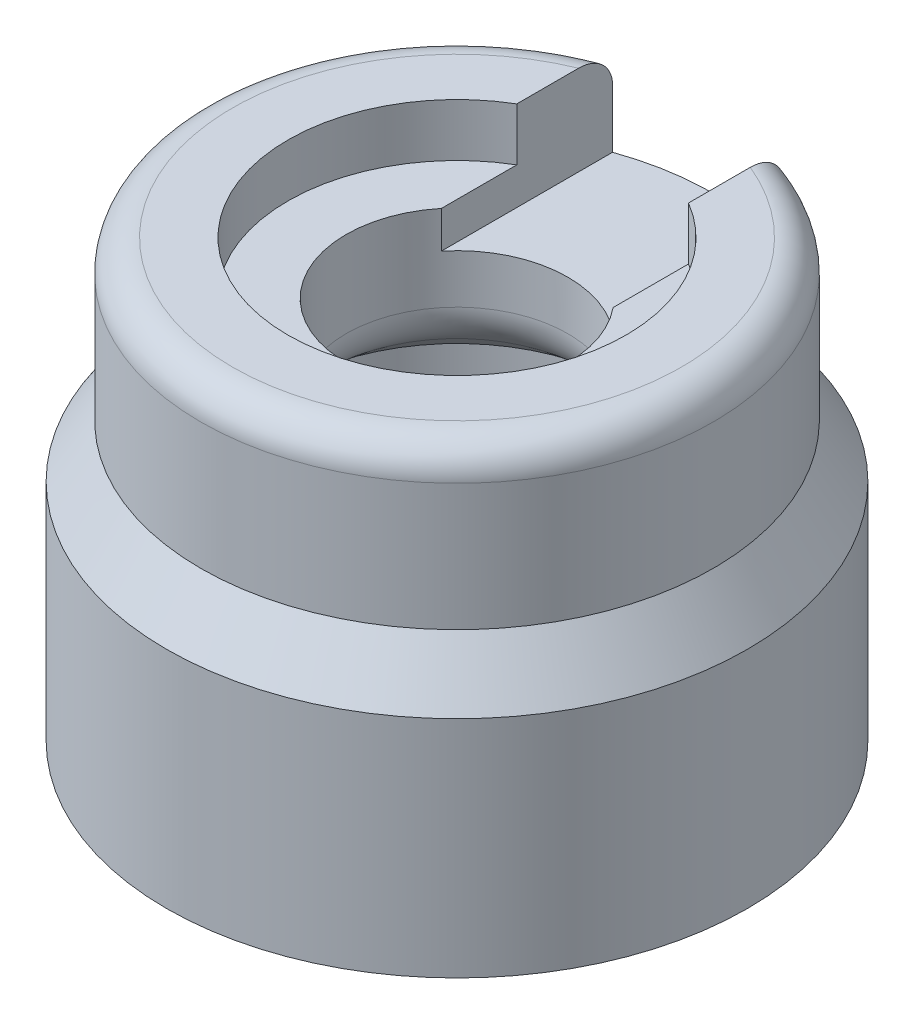
SolidWorks part; units mm, degrees
material "ABS"
ref_plane "Alzado" through (0, 0, 0) normal (0, 0, 1) x (1, 0, 0)
ref_plane "Planta" through (0, 0, 0) normal (0, 1, 0) x (1, 0, 0)
ref_plane "Vista lateral" through (0, 0, 0) normal (1, 0, 0) x (0, 0, -1)
sketch "Croquis1" plane through (0, 0, 0) normal (0, 1, 0) x (1, 0, 0)
  circle A0 centre (0, 0) radius 3.2
  circle A1 centre (0, 0) radius 5.5
  dimension "D1" = 11
  dimension "D2" = 6.4
extrude "Saliente-Extruir1" add sketch "Croquis1" along normal blind 4.25
sketch "Croquis2" plane through (0, 0, 0) normal (0, 0, 1) x (1, 0, 0)
  line L0 (-5.5, 4.25) -> (-4.85, 5.25)
  line L1 (-4.85, 5.25) -> (-2.1, 5.25)
  line L2 (-2.1, 5.25) -> (-2.1, 5.15)
  line L3 (-2.1, 5.15) -> (-3.2, 4.25)
  line L4 (5.5, 4.25) -> (-5.5, 4.25) construction
  line L5 (0, 0) -> (0, 6.8987) construction
  line L6 (-5.5, 4.25) -> (-3.2, 4.25)
  dimension "D1" = 4.2
  dimension "D2" = 0.1
  dimension "D3" = 2.75
  dimension "D4" = 1
revolve "Revolución1" add sketch "Croquis2" angle 360 about L5
sketch "Croquis3" plane through (0, 5.25, 0) normal (0, 1, 0) x (1, 0, 0)
  circle A0 centre (0, 0) radius 2.1
  circle A1 centre (0, 0) radius 4.85
  circle A2 centre (0, 0) radius 4.85 construction
  circle A3 centre (0, 0) radius 2.1 construction
extrude "Saliente-Extruir2" add sketch "Croquis3" along normal blind 3
fillet "Redondeo1" radius 0.6 1 edges at (0, 8.25, 4.85)
sketch "Croquis4" plane through (0, 8.25, 0) normal (0, 1, 0) x (1, 0, 0)
  circle A0 centre (0, 0) radius 3.2
  dimension "D1" = 6.4
extrude "Cortar-Extruir1" cut sketch "Croquis4" against normal blind 1
sketch "Croquis5" plane through (0, 7.25, 0) normal (0, 1, 0) x (1, 0, 0)
  line L1 (-1.625, 0.0031) -> (1.625, 0.0031)
  line L2 (-1.625, 0.0031) -> (-1.625, 5.0031)
  line L3 (-1.625, 5.0031) -> (1.625, 5.0031)
  line L4 (1.625, 0.0031) -> (1.625, 5.0031)
  point P4 (0, 5.0031)
  dimension "D1" = 3.25
  dimension "D2" = 5
extrude "Cortar-Extruir2" cut sketch "Croquis5" along normal through all from offset 0.7 offset against normal yes
fillet "Redondeo2" radius 1 1 edges at (0, 5.15, -2.1)
fillet "Redondeo3" radius 0.75 1 edges at (0, 0, 3.2)
